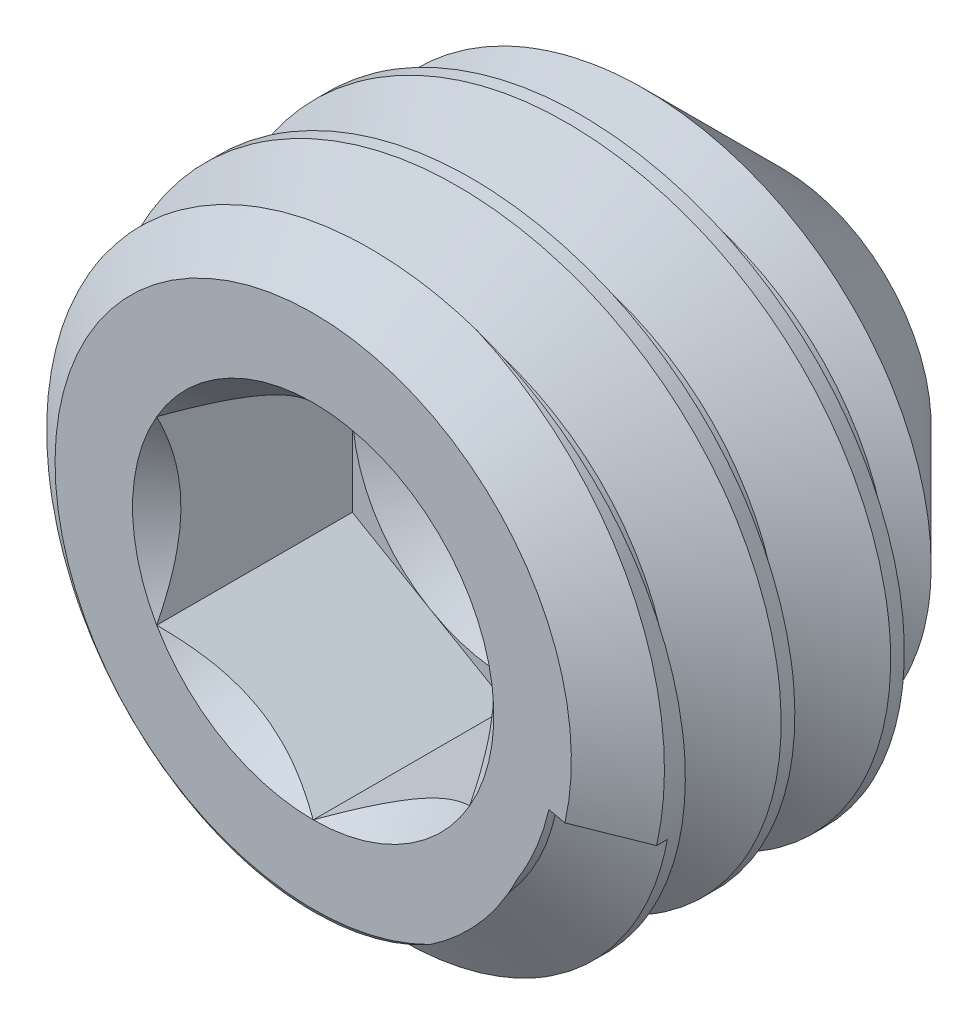
SolidWorks part; units mm, degrees
other "Imported1" parameters "D3"=3.3, "D1"=46.842, "Length"=3, "Drive Size"=2, "Thread Size"=4, "Thread Pitch"=0.7, "D2"=0.0866, "hex Depth"=1.25, "Dia"=12, "D4"=2.3829, "Cup Point Dia"=3.3528, "D5"=1.436, "D6"=1.4986, "D7"=5.0014, "Pitch"=1.75
ref_plane "Front" through (0, 0, 0) normal (0, 0, 1) x (1, 0, 0)
ref_plane "Top" through (0, 0, 0) normal (0, 1, 0) x (1, 0, 0)
ref_plane "Right" through (0, 0, 0) normal (1, 0, 0) x (0, 0, -1)
sketch "Sketch1" plane through (0, 0, 0) normal (1, 0, 0) x (0, 0, -1)
  line L0 (1.5, 2) -> (-1.5, 2) construction
  line L1 (-1.5, 2) -> (-1.5, -2) construction
  line L2 (-1.5, -2) -> (1.5, -2) construction
  line L3 (1.5, -2) -> (1.5, 2) construction
  line L4 (-1.5, 1) -> (-1.5, -1) construction
  line L5 (1.4562, 2.0758) -> (2.1562, 2.0758) construction
  line L6 (1.4562, 2.0758) -> (1.5, 2) construction
  line L7 (1.5, 2) -> (2.1125, 2) construction
  line L8 (2.1125, 2) -> (2.1562, 2.0758) construction
  line L9 (1.5, 2) -> (1.8062, 1.4696) construction
  line L10 (1.8062, 1.4696) -> (2.1125, 2) construction
  line L11 (1.7625, 1.5453) -> (1.85, 1.5453) construction
  line L12 (1.8062, 2.0758) -> (1.8062, 2) construction
  line L13 (1.8062, 1.5453) -> (1.8062, 1.4696) construction
  point P3 (0, 2)
  point P24 (-1.5, 0)
  point P25 (-1.5, 0)
  dimension "D1" = 0.0875
sketch "Sketch11" plane through (0, 0, 0) normal (1, 0, 0) x (0, 0, -1)
  line L0 (-1.5, 0) -> (-1.5, 1.65)
  line L1 (-1.5, 1.65) -> (-1.2549, 2)
  line L2 (-1.2549, 2) -> (0.45, 2)
  line L3 (0.45, 2) -> (1.5, 0.95)
  line L4 (1.5, 0.95) -> (0.9292, 0)
  line L5 (0.9292, 0) -> (-1.5, 0)
  line L6 (0.9292, 0) -> (1.5, 0) construction
  line L7 (1.5, 0) -> (1.5, 0.95) construction
  line L8 (1.5, -0.95) -> (0.9292, 0) construction
  line L9 (-1.2549, -2) -> (0.45, -2) construction
  line L10 (-1.5, -2) -> (1.5, -2) construction
  line L11 (-1.5, 2) -> (-1.5, -2) construction
  line L12 (1.5, -2) -> (1.5, 2) construction
  point P11 (-0.95, -2)
  point P12 (-1.5, 2)
  dimension "D3" = 35
  dimension "D5" = 118
  dimension "D6" = 45
  dimension "D1" = 0.35
  dimension "D2" = 2.45
  dimension "D4" = 1.05
revolve "Revolve1" add sketch "Sketch11" angle 360 about L6
sketch "Sketch2" plane through (0, 0, 1.5) normal (0, 0, 1) x (1, 0, 0)
  line L1 (0, 1.1547) -> (-1, 0.5774)
  line L2 (-1, 0.5774) -> (-1, -0.5774)
  line L3 (-1, -0.5774) -> (0, -1.1547)
  line L4 (0, -1.1547) -> (1, -0.5774)
  line L5 (1, -0.5774) -> (1, 0.5774)
  line L6 (1, 0.5774) -> (0, 1.1547)
  circle A0 centre (0, 0) radius 1 construction
  circle A1 centre (0, 0) radius 2 construction
extrude "Cut-Extrude1" cut sketch "Sketch2" against normal blind 1.25
sketch "Sketch3" plane through (0, 0, 1.5) normal (0, 0, 1) x (1, 0, 0)
  circle A0 centre (0, 0) radius 1.1547
extrude "Cut-Extrude2" cut sketch "Sketch3" against normal through all draft 45
sketch "Sketch4" plane through (0, 0, 0.25) normal (0, 0, 1) x (1, 0, 0)
  circle A0 centre (0, 0) radius 1 construction
  circle A1 centre (0, 0) radius 1
extrude "Cut-Extrude3" cut sketch "Sketch4" against normal through all draft 60
sketch "Sketch13" plane through (0, 0, 0) normal (1, 0, 0) x (0, 0, -1)
  line L0 (0, -2) -> (0, 2) construction
  line L2 (-1.2549, 2) -> (0.45, 2) construction
  line L4 (0.9292, 0) -> (-1.5, 0) construction
  point P0 (-3.0708, 0)
  point P4 (0, 0)
  point P9 (3.0708, 0)
  dimension "D1" = 4
ref_plane "Plane1" through (0, 0, -1.5) normal (0, 0, 1) x (1, 0, 0)
sketch "Sketch5" plane through (0, 0, -1.5) normal (0, 0, 1) x (1, 0, 0)
  circle A0 centre (0, 0) radius 2 construction
  circle A1 centre (0, 0) radius 2
curve "Helix/Spiral1" pitch 0.7 height 3.3 radius 2 centre (0, 0, -1.5) axis (0, 0, 1) start towards (0, 1, 0)
sketch "Sketch6" plane through (0, 0, 0) normal (1, 0, 0) x (0, 0, -1)
  line L0 (1.4781, 2.0379) -> (2.1344, 2.0379)
  line L1 (1.4562, 2.0758) -> (1.5, 2) construction
  line L2 (2.1125, 2) -> (2.1562, 2.0758) construction
  line L3 (2.1344, 2.0379) -> (1.85, 1.5453)
  line L4 (1.85, 1.5453) -> (1.7625, 1.5453)
  line L5 (1.7625, 1.5453) -> (1.4781, 2.0379)
sweep "Cut-Sweep1" cut profiles "Sketch6" path "Helix/Spiral1"
equation "\"D3@Helix/Spiral1\" = \"Length@Sketch1\" * 1.1"
equation "\"hex Depth@Cut-Extrude1\"=\"Drive Size@Sketch1\" * .625"
equation "\"D1@Sketch11\" = \"Thread Pitch@Sketch1\" * .5"
equation "\"D2@Sketch11\" = \"Thread Pitch@Sketch1\" * 3.5"
equation "\"D1@Helix/Spiral1\" = \"Thread Pitch@Sketch1\""
equation "\"D4@Sketch11\" = \"Thread Pitch@Sketch1\" * 1.5"
equation "\"D1@Sketch1\" = \"Thread Pitch@Sketch1\" / 8"
equation "\"D1@Sketch13\"=\"Thread Size@Sketch1\""
